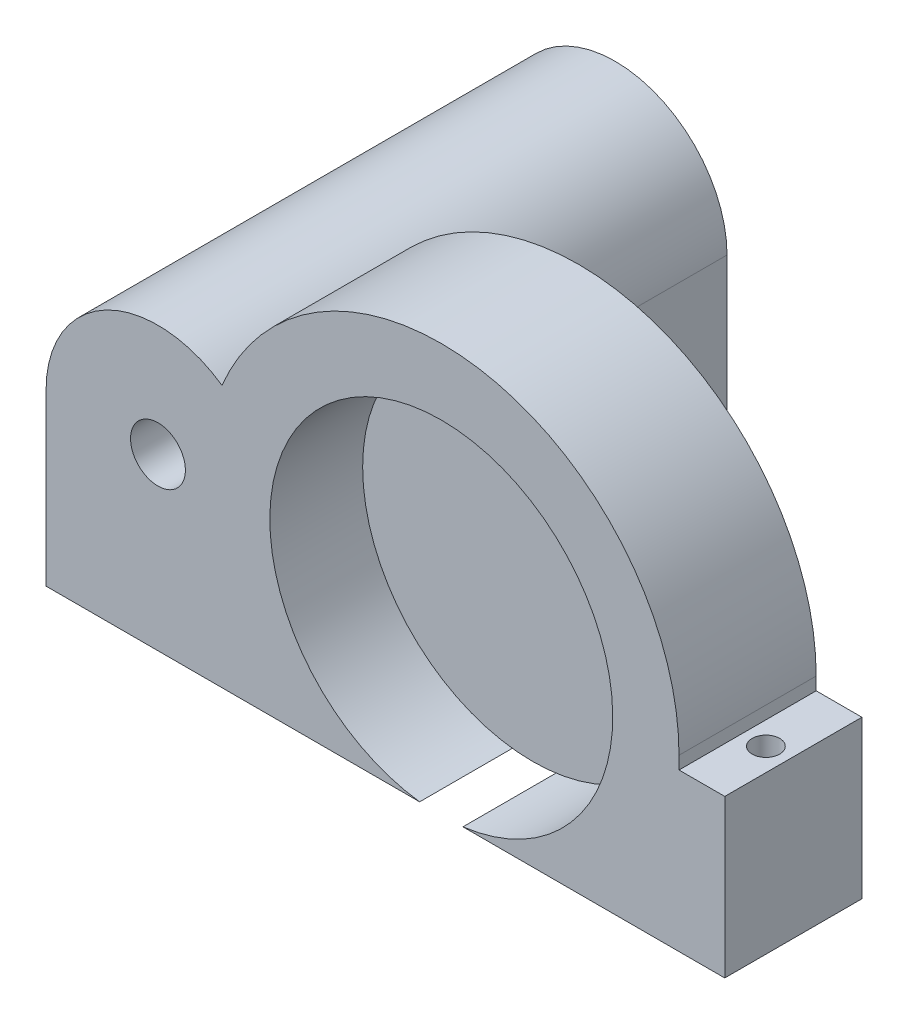
SolidWorks part; units mm, degrees
ref_plane "Front Plane" through (0, 0, 0) normal (0, 0, 1) x (1, 0, 0)
ref_plane "Top Plane" through (0, 0, 0) normal (0, 1, 0) x (1, 0, 0)
ref_plane "Right Plane" through (0, 0, 0) normal (1, 0, 0) x (0, 0, -1)
sketch "Sketch1" plane through (0, 0, 0) normal (0, 0, 1) x (1, 0, 0)
  line L0 (11, 0) -> (-11, 0) construction
  line L1 (0, -18.6) -> (-26, -18.6) construction
  line L2 (-26, 0) -> (-26, -1.4011)
  line L4 (-26, -1.4011) -> (-26, -18.6)
  line L5 (26, 0) -> (26, -1.4011)
  line L6 (26, -1.4011) -> (31, -1.4011)
  line L7 (31, -1.4011) -> (31, -18.6)
  line L8 (-26, -18.6) -> (31, -18.6)
  line L10 (0, -55) -> (0, 55) construction
  circle A0 centre (0, 0) radius 18.6
  circle A1 centre (0, 0) radius 18.75
  arc A2 (-26, 0) -> (26, 0) centre (0, 0) cw
  dimension "D1" = 37.5
  dimension "R1" = 37.2
  dimension "D2" = 26
extrude "Boss-Extrude1" add sketch "Sketch1" along normal blind 5 contours A0 region at (0, 0, 0)
extrude "Boss-Extrude2" add sketch "Sketch1<3>" along normal blind 15 separate body contours A2 L2 L4 L8 L7 L6 L5 A1 region at (0, 25.2762, 0)
sketch "Sketch1<3>" plane through (0, 0, 0) normal (0, 0, 1) x (1, 0, 0) same geometry as "Sketch1"
sketch "Sketch2" plane through (0, 0, 0) normal (0, 1, 0) x (1, 0, 0)
  line L0 (-24.53, 0) -> (24.53, 0) construction
  line L2 (31, -15) -> (31, 0) construction
  circle A0 centre (-28.5, -8) radius 1.5
  circle A1 centre (28.5, -8) radius 1.5
  dimension "D1" = 3
  dimension "D2" = 8
  dimension "D4" = 2.5
extrude "Cut-Extrude1" cut sketch "Sketch2" against normal blind 20
sketch "Sketch3" plane through (0, 0, 0) normal (0, 0, 1) x (1, 0, 0)
  line L0 (11, 0) -> (-11, 0) construction
  line L1 (-43.2196, 0) -> (-43.2196, -18.6)
  line L2 (-43.2196, -18.6) -> (-24.5251, -18.6)
  line L3 (-18.75, 0) -> (-18.75, -18.6)
  line L4 (-26, -18.6) -> (-2.367, -18.6) construction
  line L6 (-18.75, -18.6) -> (-24.5251, -18.6)
  circle A0 centre (-30.9848, 0) radius 3
  arc A1 (-43.2196, 0) -> (-18.75, 0) centre (-30.9848, 0) cw
  arc A2 (2.367, -18.6) -> (-2.367, -18.6) centre (0, 0) ccw construction
  dimension "D1" = 6
extrude "Boss-Extrude3" add sketch "Sketch3" along normal blind 50 from offset 35 contours A1 L1 L2 L3 A0 region at (-30.9848, -4.5496, 0) offset against normal yes
